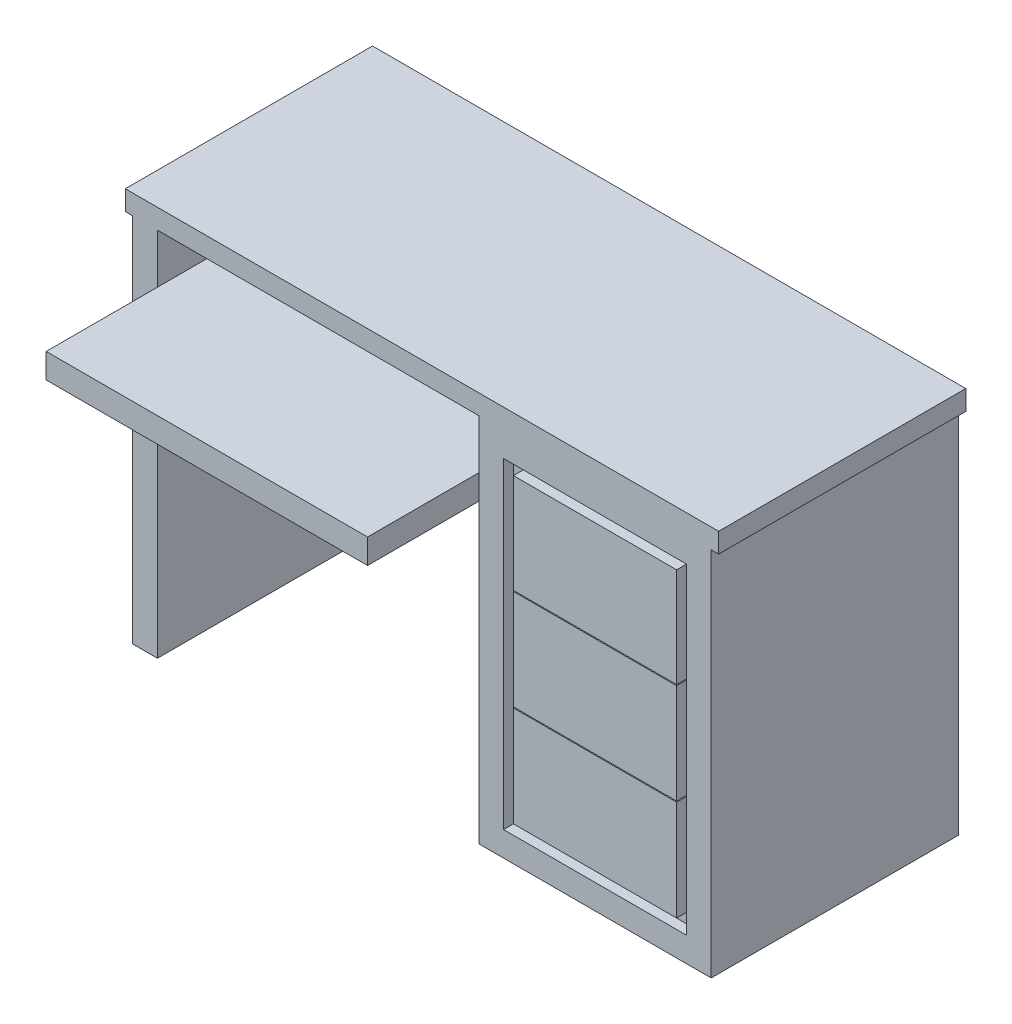
SolidWorks part; units mm, degrees
ref_plane "Front Plane" through (0, 0, 0) normal (0, 0, 1) x (1, 0, 0)
ref_plane "Top Plane" through (0, 0, 0) normal (0, 1, 0) x (1, 0, 0)
ref_plane "Right Plane" through (0, 0, 0) normal (1, 0, 0) x (0, 0, -1)
sketch "Sketch1" plane through (0, 0, 0) normal (0, 1, 0) x (1, 0, 0)
  line L0 (0, 0) -> (1200, 0)
  line L1 (0, 0) -> (0, 500)
  line L2 (0, 500) -> (1200, 500)
  line L3 (1200, 500) -> (1200, 0)
  dimension "D1" = 1200
  dimension "D2" = 500
extrude "Boss-Extrude1" add sketch "Sketch1" along normal blind 40 contours L3 L0 L1 L2
sketch "Sketch2" plane through (0, 0, 0) normal (0, -1, 0) x (1, 0, 0)
  line L0 (0, 0) -> (15, 0) construction
  line L1 (0, 0) -> (1200, 0) construction
  line L2 (15, 0) -> (15, -500)
  line L3 (0, -500) -> (1200, -500) construction
  line L4 (15, -500) -> (65, -500)
  line L5 (15, 0) -> (65, 0)
  line L6 (65, 0) -> (65, -500)
  line L7 (600, 0) -> (600, -500) construction
  line L8 (1185, 0) -> (1135, 0)
  line L9 (1185, 0) -> (1185, -500)
  line L10 (1185, -500) -> (1135, -500)
  line L11 (1135, 0) -> (1135, -500)
  dimension "D1" = 15
  dimension "D2" = 50
extrude "Boss-Extrude2" add sketch "Sketch2" along normal blind 750
sketch "Sketch3" plane through (0, 0, 0) normal (0, 0, 1) x (1, 0, 0)
  line L0 (65, 0) -> (65, -100) construction
  line L1 (65, -750) -> (65, 0) construction
  line L2 (65, -100) -> (65, -150)
  line L3 (65, -100) -> (715, -100)
  line L4 (65, -150) -> (715, -150)
  line L5 (715, -150) -> (715, -100)
  dimension "D1" = 100
  dimension "D2" = 50
  dimension "D3" = 650
extrude "Boss-Extrude3" add sketch "Sketch3" along normal mid plane 450
sketch "Sketch4" plane through (0, 0, 0) normal (0, -1, 0) x (1, 0, 0)
  line L0 (715, 0) -> (765, 0)
  line L1 (715, 225) -> (715, -225) construction
  line L2 (65, 0) -> (1135, 0) construction
  line L3 (715, 0) -> (715, -500)
  line L4 (65, -500) -> (1135, -500) construction
  line L5 (715, -500) -> (765, -500)
  line L6 (765, -500) -> (765, 0)
  dimension "D1" = 50
extrude "Boss-Extrude4" add sketch "Sketch4" along normal blind 750
sketch "Sketch5" plane through (0, 0, 0) normal (0, 0, 1) x (1, 0, 0)
  line L0 (765, 0) -> (765, -50)
  line L1 (765, -750) -> (765, 0) construction
  line L2 (765, -50) -> (1135, -50)
  line L3 (1135, -750) -> (1135, 0) construction
  line L4 (1135, -50) -> (1135, 0)
  line L5 (1135, 0) -> (765, 0)
  line L6 (1135, -375) -> (765, -375) construction
  line L7 (1135, -700) -> (1135, -750)
  line L8 (765, -700) -> (1135, -700)
  line L9 (765, -750) -> (765, -700)
  line L10 (1135, -750) -> (765, -750)
  dimension "D1" = 50
extrude "Boss-Extrude5" add sketch "Sketch5" against normal blind 500
sketch "Sketch6" plane through (0, 0, -500) normal (0, 0, -1) x (-1, 0, 0)
  line L1 (-1135, -50) -> (-765, -50)
  line L2 (-1135, -50) -> (-1135, -700)
  line L3 (-1135, -700) -> (-765, -700)
  line L4 (-765, -50) -> (-765, -700)
extrude "Boss-Extrude6" add sketch "Sketch6" against normal blind 50
sketch "Sketch7" plane through (0, 0, 0) normal (0, 0, 1) x (1, 0, 0)
  line L0 (765, -50) -> (785, -50) construction
  line L1 (765, -50) -> (1135, -50) construction
  line L2 (765, -50) -> (765, -70) construction
  line L3 (765, -700) -> (765, -50) construction
  line L4 (1135, -700) -> (1135, -680) construction
  line L5 (1135, -700) -> (1135, -50) construction
  line L6 (1135, -700) -> (1115, -700) construction
  line L7 (1135, -700) -> (765, -700) construction
  line L8 (1115, -70) -> (1115, -273)
  line L9 (785, -70) -> (1115, -70)
  line L11 (785, -680) -> (1115, -680)
  line L13 (1115, -273) -> (785, -273)
  line L14 (1115, -477) -> (785, -477)
  line L15 (785, -70) -> (785, -680)
  line L16 (1115, -680) -> (1115, -477)
  line L17 (1115, -477) -> (1115, -273)
  dimension "D1" = 20
  dimension "D2" = 203
  dimension "D3" = 203
extrude "Boss-Extrude7" add sketch "Sketch7" against normal blind 450 contours L9 L15 L13 L8 | L14 L17 L13 L15 | L11 L16 L14 L15 region at (950, -171.5, 0) region at (950, -375, 0) region at (950, -578.5, 0)
sketch "Sketch9" plane through (0, 0, -450) normal (0, 0, 1) x (1, 0, 0)
sketch "Sketch13" plane through (0, 0, 0) normal (0, 0, 1) x (1, 0, 0)
  line L1 (785, -70) -> (1115, -70)
  line L2 (785, -70) -> (785, -680)
  line L3 (785, -680) -> (1115, -680)
  line L4 (1115, -70) -> (1115, -680)
  line L5 (1135, -700) -> (765, -700)
  line L6 (1135, -700) -> (1135, -50)
  line L7 (1135, -50) -> (765, -50)
  line L8 (765, -700) -> (765, -50)
extrude "Boss-Extrude9" add sketch "Sketch13" against normal blind 450
extrude "Cut-Extrude1" cut sketch "Sketch13<3>" against normal blind 20
sketch "Sketch13<3>" plane through (0, 0, 0) normal (0, 0, 1) x (1, 0, 0) same geometry as "Sketch13"
sketch "Sketch14" plane through (0, 0, 0) normal (0, 0, 1) x (1, 0, 0)
  line L2 (1115, -680) -> (1115, -70) construction
  line L5 (1115, -273) -> (785, -273)
  line L6 (785, -70) -> (785, -680) construction
  line L7 (1115, -477) -> (785, -477)
  line L8 (785, -70) -> (785, -680) construction
extrude "Cut-Extrude-Thin1" cut sketch "Sketch14" against normal blind 450 thin thin type one direction wall 2
